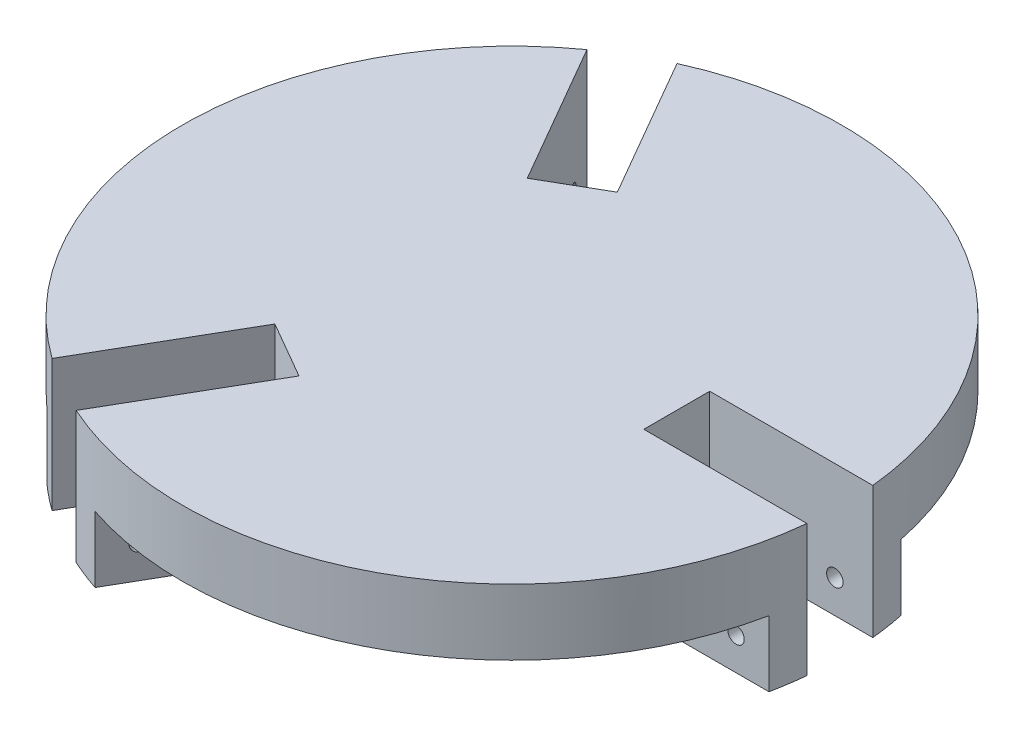
SolidWorks part; units mm, degrees
ref_plane "Plan de face" through (0, 0, 0) normal (0, 0, 1) x (1, 0, 0)
ref_plane "Plan de dessus" through (0, 0, 0) normal (0, 1, 0) x (1, 0, 0)
ref_plane "Plan de droite" through (0, 0, 0) normal (1, 0, 0) x (0, 0, -1)
sketch "Esquisse1" plane through (0, 0, 0) normal (0, 1, 0) x (1, 0, 0)
  circle A0 centre (0, 0) radius 50
  dimension "D1" = 100
extrude "Boss.-Extru.1" add sketch "Esquisse1" along normal mid plane 10
sketch "Esquisse2" plane through (0, 5, 0) normal (0, 1, 0) x (1, 0, 0)
  line L0 (0, 0) -> (50, 0) construction
  line L5 (25, 5) -> (50, 5)
  line L6 (25, 5) -> (25, -5)
  line L7 (25, -5) -> (50, -5)
  line L8 (50, 5) -> (50, -5)
  circle A0 centre (0, 0) radius 50 construction
  point P10 (0, 0)
  dimension "D1" = 5
  dimension "D2" = 5
  dimension "D3" = 25
extrude "Enlèv. mat.-Extru.1" cut sketch "Esquisse2" against normal through all
pattern_circular "Répétition circulaire" count 3 over 360 about axis through (0, 5, 0) along (0, 1, 0) of "Enlèv. mat.-Extru.1"
sketch "Esquisse3" plane through (0, -5, 0) normal (0, -1, 0) x (1, 0, 0)
  line L0 (48.9898, 10) -> (20, 10)
  line L1 (20, 10) -> (20, -10)
  line L2 (20, -10) -> (48.9898, -10)
  line L3 (49.7494, -5) -> (25, -5)
  line L4 (25, -5) -> (25, 5)
  line L5 (25, 5) -> (49.7494, 5)
  arc A0 (49.7494, 5) -> (48.9898, 10) centre (0, 0) ccw
  arc A1 (-20.5446, -45.5842) -> (49.7494, -5) centre (0, 0) ccw construction
  arc A2 (48.9898, -10) -> (49.7494, -5) centre (0, 0) ccw
  dimension "D1" = 5
  dimension "D2" = 5
  dimension "D3" = 5
extrude "Boss.-Extru.2" add sketch "Esquisse3" along normal blind 10
pattern_circular "Répétition circulaire1" count 3 over 360 about axis through (0, -5, 0) along (0, 1, 0) of "Boss.-Extru.2"
sketch "Esquisse4" plane through (0, 0, -10) normal (0, 0, -1) x (-1, 0, 0)
  line L0 (-20, -15) -> (-48.9898, -15) construction
  line L1 (-48.9898, -15) -> (-48.9898, -5) construction
  point P0 (-43.9898, -10)
  point P1 (-28.9898, -10)
  dimension "D1" = 5
  dimension "D2" = 15
  dimension "D3" = 5
hole_wizard "Trou taraudé M31" positions "Esquisse4" profile "Esquisse5" tap size "M3" standard "ISO" end condition through all
sketch "Esquisse5" plane through (43.9898, -10, -10) normal (1, 0, 0) x (0, 1, 0)
  line L0 (0, 0) -> (0, 60)
  line L1 (0, 60) -> (1.25, 60)
  line L2 (1.25, 60) -> (1.25, 0)
  line L5 (1.25, 0) -> (0, 0)
  line L11 (0, -6.35) -> (0, 107.95) construction
  dimension "Diamètre du trou pour taraudage jusqu'au prochain" = 2.5
  dimension "Profondeur du trou pour taraudage jusqu'au prochain" = 60
cosmetic thread "Filetage de perçage1" parameters "D2"=3
cosmetic thread "Filetage de perçage2" parameters "D2"=3
pattern_circular "Répétition circulaire2" count 3 over 360 about axis through (0, 5, 0) along (0, 1, 0) of "Trou taraudé M31"
cosmetic thread "Filetage de perçage3" parameters "D2"=3
cosmetic thread "Filetage de perçage4" parameters "D2"=3
cosmetic thread "Filetage de perçage5" parameters "D2"=3
cosmetic thread "Filetage de perçage6" parameters "D2"=3
